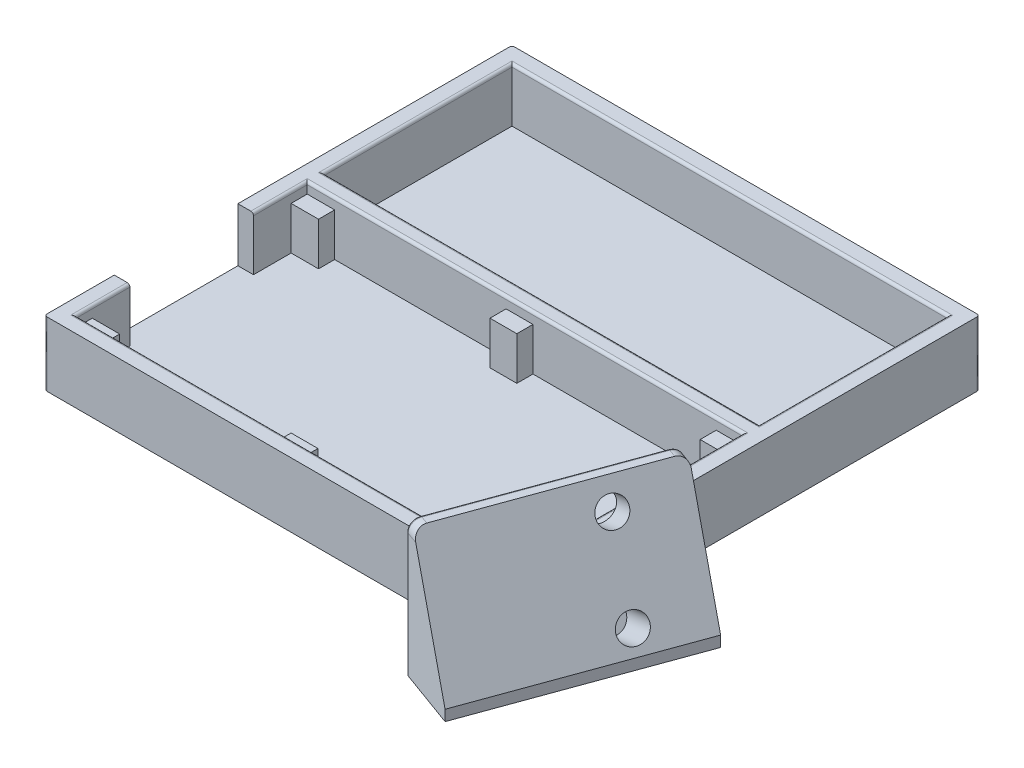
SolidWorks part; units mm, degrees
note: The reader was unsure of these and kept them because the rebuilt part matched: shared geometry of "Sketch1<4>".
ref_plane "Front Plane" through (0, 0, 0) normal (0, 0, 1) x (1, 0, 0)
ref_plane "Top Plane" through (0, 0, 0) normal (0, 1, 0) x (1, 0, 0)
ref_plane "Right Plane" through (0, 0, 0) normal (1, 0, 0) x (0, 0, -1)
sketch "Sketch1" plane through (0, 0, 0) normal (0, 1, 0) x (1, 0, 0)
  line L0 (8, 46) -> (39.9, 46)
  line L1 (0, 0) -> (87, 0)
  line L2 (0, 0) -> (0, 49)
  line L3 (0, 49) -> (87, 49)
  line L4 (87, 0) -> (87, 49)
  line L5 (8, 3) -> (39.9, 3)
  line L6 (0, 36) -> (2.9, 36)
  line L7 (2.9, 36) -> (2.9, 43)
  line L8 (2.9, 6) -> (2.9, 13)
  line L9 (2.9, 13) -> (0, 13)
  line L10 (83.9, 43) -> (83.9, 6)
  line L11 (3, 49) -> (3, 84)
  line L12 (73, 0) -> (84, -12)
  line L13 (84, -12) -> (87, 0)
  line L14 (39.9, 46) -> (39.9, 43)
  line L15 (39.9, 43) -> (44.9, 43)
  line L16 (44.9, 43) -> (44.9, 46)
  line L17 (44.9, 46) -> (79, 46)
  line L18 (39.9, 3) -> (39.9, 6)
  line L19 (39.9, 6) -> (44.9, 6)
  line L20 (44.9, 6) -> (44.9, 3)
  line L21 (44.9, 3) -> (79, 3)
  line L22 (79, 3) -> (79, 6)
  line L23 (79, 6) -> (83.9, 6)
  line L24 (79, 46) -> (79, 43)
  line L25 (79, 43) -> (83.9, 43)
  line L26 (8, 46) -> (8, 43)
  line L27 (8, 43) -> (2.9, 43)
  line L28 (8, 3) -> (8, 6)
  line L29 (8, 6) -> (2.9, 6)
  line L30 (0, 49) -> (87, 49)
  line L31 (0, 49) -> (0, 87)
  line L32 (0, 87) -> (87, 87)
  line L33 (87, 49) -> (87, 87)
  line L34 (3, 84) -> (84, 84)
  line L35 (84, 84) -> (84, 49)
sketch "Sketch2" plane through (0, 0, 0) normal (0, 0, 1) x (1, 0, 0)
  line L0 (90, 0) -> (102, 0)
  line L1 (102, 0) -> (102, 2)
  line L2 (102, 2) -> (92, 25)
  line L3 (92, 25) -> (90, 25)
  line L4 (90, 25) -> (90, 0)
extrude "Boss-Extrude1" add sketch "Sketch2" along normal blind 40
move or copy body "Body-Move/Copy1" bodies to move or copy 101 copy no rotation origin (95, 0, 20) rotation axis (0, -1, 0) rotation angle 20
move or copy body "Body-Move/Copy2" bodies to move or copy 102 copy no translate (-4, 0, -25) parameters "D1"=4, "D2"=0, "D3"=25
extrude "Boss-Extrude2" add sketch "Sketch1" along normal blind 2
extrude "Boss-Extrude3" add sketch "Sketch1<4>" along normal blind 12 contours L0 L10 L5 L8 L9 L2 L1 L4 L3 L6 L7 | L34 L35 L30 L33 L32 L31 L3 L11
sketch "Sketch1<4>" plane through (0, 0, 0) normal (0, 1, 0) x (1, 0, 0) same geometry as "Sketch1"
sketch "Sketch4" plane through (72.4478, 33.5206, 26.3688) normal (0.8618, 0.3987, 0.3137) x (0.3002, 0.0976, -0.9489)
  line L0 (12.0749, -35.8595) -> (39.9159, -38.8391) construction
  line L1 (12.0749, -35.8595) -> (51.8478, -40.1161) construction
  line L2 (48.1735, -39.7229) -> (50.5995, -17.0548) construction
  line L3 (39.9159, -38.8391) -> (40.3416, -34.8618) construction
  line L4 (40.3416, -34.8618) -> (42.0442, -18.9527) construction
  circle A3 centre (42.0442, -18.9527) radius 2.5
  circle A4 centre (40.3416, -34.8618) radius 2.5
extrude "Cut-Extrude2" cut sketch "Sketch4" against normal blind 8
fillet "Fillet1" radius 2 2 edges at (94.0816, 25, -25.1619) (80.4008, 25, 12.4258)
sketch "Sketch10" plane through (0, 12, 0) normal (0, 1, 0) x (1, 0, 0)
  line L5 (83.9, 6) -> (79, 6)
  line L11 (39.9, 3) -> (45, 3)
  line L12 (39.9, 3) -> (39.9, 6)
  line L13 (39.9, 6) -> (45, 6)
  line L14 (45, 3) -> (45, 6)
  line L15 (39.9, 46) -> (44.9, 46)
  line L16 (39.9, 46) -> (39.9, 43)
  line L17 (39.9, 43) -> (44.9, 43)
  line L18 (44.9, 46) -> (44.9, 43)
  line L32 (83.9, 6) -> (83.9, 3)
  line L33 (83.9, 3) -> (79, 3)
  line L39 (79, 6) -> (79, 3)
  line L40 (83.9, 43) -> (79, 43)
  line L41 (83.9, 43) -> (83.9, 46)
  line L42 (83.9, 46) -> (79, 46)
  line L43 (79, 43) -> (79, 46)
  line L44 (8, 46) -> (2.9, 46)
  line L45 (8, 46) -> (8, 43)
  line L46 (8, 43) -> (2.9, 43)
  line L47 (2.9, 46) -> (2.9, 43)
  line L48 (8, 3) -> (2.9, 3)
  line L49 (8, 3) -> (8, 6)
  line L50 (8, 6) -> (2.9, 6)
  line L51 (2.9, 3) -> (2.9, 6)
extrude "Cut-Extrude4" cut sketch "Sketch10" against normal blind 2
fillet "Fillet2" radius 0.5 17 edges at (2.9, 12, -8) (2.9, 12, -41) (0, 6, 0) (92.9416, 24.4142, -24.9535) (86.3015, 25, -6.7101) (79.6615, 24.4142, 11.5333) (93.1419, 11.5, -25.504) (79.4611, 11.5, 12.0838) (43.4, 12, -3) (83.9, 12, -24.5) (43.4, 12, -46) (43.5, 12, -84) (84, 12, -66.5) (43.5, 12, -49) (3, 12, -66.5) (0, 6, -87) (87, 6, -87)
